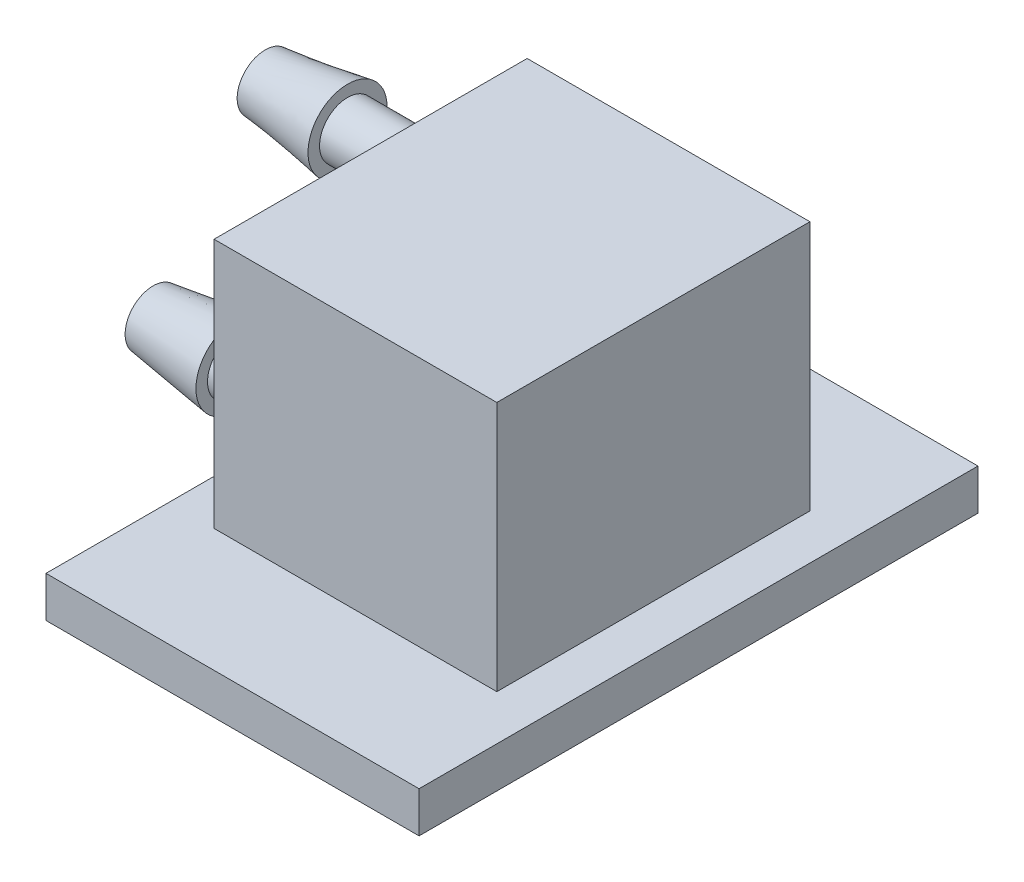
SolidWorks part; units mm, degrees
ref_plane "Front Plane" through (0, 0, 0) normal (0, 0, 1) x (1, 0, 0)
ref_plane "Top Plane" through (0, 0, 0) normal (0, 1, 0) x (1, 0, 0)
ref_plane "Right Plane" through (0, 0, 0) normal (1, 0, 0) x (0, 0, -1)
sketch "Sketch1" plane through (0, 0, 0) normal (0, 1, 0) x (1, 0, 0)
  line L1 (0, 0) -> (10.8966, 0)
  line L2 (0, 0) -> (0, 12.065)
  line L3 (0, 12.065) -> (10.8966, 12.065)
  line L4 (10.8966, 0) -> (10.8966, 12.065)
  dimension "D1" = 12.065
  dimension "D2" = 10.8966
extrude "Boss-Extrude1" add sketch "Sketch1" along normal blind 9.652
sketch "Sketch2" plane through (0, 0, 0) normal (-1, 0, 0) x (0, 0, 1)
  line L0 (-8.1915, 8.763) -> (-1.8359, 8.763) construction
  line L1 (-12.065, 9.652) -> (0, 9.652) construction
  line L2 (-3.8735, 0.889) -> (-9.0509, 0.889) construction
  line L3 (-8.1915, 8.763) -> (-8.1915, 9.652) construction
  line L4 (-3.8735, 0.889) -> (-3.8735, 0) construction
  line L5 (-12.065, 0) -> (0, 0) construction
  line L6 (-8.1915, 7.6835) -> (-12.065, 7.6835) construction
  line L7 (-12.065, 9.652) -> (-12.065, 0) construction
  line L8 (-3.8735, 1.9685) -> (0, 1.9685) construction
  line L9 (0, 9.652) -> (0, 0) construction
  circle A0 centre (-8.1915, 7.6835) radius 1.0795
  circle A1 centre (-3.8735, 1.9685) radius 1.0795
  dimension "D1" = 2.159
  dimension "D2" = 0.889
  dimension "D3" = 4.318
extrude "Boss-Extrude2" add sketch "Sketch2" along normal blind 3.048
sketch "Sketch3" plane through (-3.048, 0, 0) normal (-1, 0, 0) x (0, 0, 1)
  circle A0 centre (-8.1915, 7.6835) radius 1.524
  dimension "D1" = 3.048
ref_plane "Plane1" through (-6.223, 0, 0) normal (-1, 0, 0) x (0, 0, 1)
sketch "Sketch4" plane through (-6.223, 0, 0) normal (-1, 0, 0) x (0, 0, 1)
  circle A0 centre (-8.1915, 7.6835) radius 1.0795 construction
  circle A2 centre (-8.1915, 7.6835) radius 1.0795
loft "Loft1" add profiles "Sketch3", "Sketch4" connector at (-3.048, 9.1532, -7.7884) connector at (-6.223, 8.4824, -7.4655)
sketch "Sketch6" plane through (-3.048, 0, 0) normal (-1, 0, 0) x (0, 0, 1)
  circle A0 centre (-3.8735, 1.9685) radius 1.524
  circle A1 centre (-8.1915, 7.6835) radius 1.524 construction
sketch "Sketch7" plane through (-6.223, 0, 0) normal (-1, 0, 0) x (0, 0, 1)
  circle A0 centre (-3.8735, 1.9685) radius 1.0795
  circle A1 centre (-8.1915, 7.6835) radius 1.0795 construction
loft "Loft2" add profiles "Sketch6", "Sketch7" connector at (-3.048, 3.3176, -3.1646) connector at (-6.223, 2.931, -3.3848)
sketch "Sketch8" plane through (0, 0, 0) normal (0, -1, 0) x (1, 0, 0)
  line L1 (12.6365, 4.7371) -> (-1.7399, 4.7371)
  line L2 (12.6365, 4.7371) -> (12.6365, -16.8021)
  line L3 (12.6365, -16.8021) -> (-1.7399, -16.8021)
  line L4 (-1.7399, 4.7371) -> (-1.7399, -16.8021)
  line L5 (7.108, 4.7371) -> (7.108, 0) construction
  line L6 (0, 0) -> (10.8966, 0) construction
  line L8 (10.8966, -12.065) -> (0, -12.065) construction
  line L9 (7.108, -12.065) -> (7.108, -16.8021) construction
  line L10 (-1.7399, -1.2371) -> (0, -1.2371) construction
  line L11 (0, -12.065) -> (0, 0) construction
  line L13 (10.8966, 0) -> (10.8966, -12.065) construction
  line L14 (10.8966, -1.2371) -> (12.6365, -1.2371) construction
  dimension "D1" = 14.3764
  dimension "D2" = 21.5392
extrude "Boss-Extrude3" add sketch "Sketch8" along normal blind 1.5748
